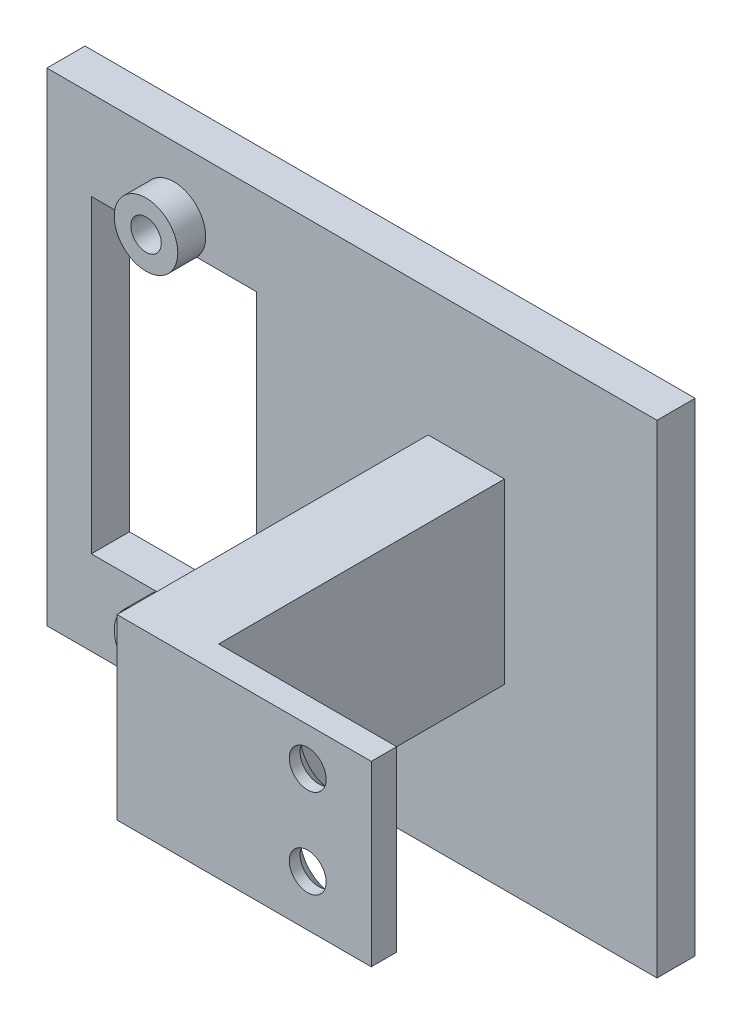
SolidWorks part; units mm, degrees
ref_plane "Front Plane" through (0, 0, 0) normal (0, 0, 1) x (1, 0, 0)
ref_plane "Top Plane" through (0, 0, 0) normal (0, 1, 0) x (1, 0, 0)
ref_plane "Right Plane" through (0, 0, 0) normal (1, 0, 0) x (0, 0, -1)
sketch "Sketch1" plane through (0, 0, 0) normal (0, 0, 1) x (1, 0, 0)
  line L1 (-70, 0) -> (-22, 0)
  line L2 (-70, 0) -> (-70, 38)
  line L3 (-70, 38) -> (-22, 38)
  line L4 (-22, 0) -> (-22, 38)
  line L6 (-66.5, 6.65) -> (-53.5, 6.65)
  line L7 (-66.5, 6.65) -> (-66.5, 31)
  line L8 (-66.5, 31) -> (-53.5, 31)
  line L9 (-53.5, 6.65) -> (-53.5, 31)
extrude "Servo_Shelf" add sketch "Sketch1" along normal blind 3 from offset 27.48 offset against normal yes
sketch "Sketch2" plane through (0, 0, 0) normal (0, 0, 1) x (1, 0, 0)
  line L1 (-40, 14) -> (-34, 14)
  line L2 (-40, 14) -> (-40, 28)
  line L3 (-40, 28) -> (-34, 28)
  line L4 (-34, 14) -> (-34, 28)
extrude "Outboard_Riser" add sketch "Sketch2" along normal blind 24.48 from offset 25.48 offset against normal yes
sketch "Sketch3" plane through (0, 0, 0) normal (0, 0, 1) x (1, 0, 0)
  line L1 (-40, 14) -> (-20, 14)
  line L2 (-40, 14) -> (-40, 28)
  line L3 (-40, 28) -> (-20, 28)
  line L4 (-20, 14) -> (-20, 28)
extrude "Plate_Attachment_Foot" add sketch "Sketch3" along normal blind 2 from offset 2 offset against normal yes
sketch "Sketch4" plane through (0, 0, -2) normal (0, 0, -1) x (-1, 0, 0)
  circle A0 centre (25, 18) radius 1.45
  circle A1 centre (25, 25) radius 1.45
extrude "Servo_Pad_D2p9" cut sketch "Sketch4" against normal blind 2.01
sketch "Sketch5" plane through (0, 0, -2) normal (0, 0, -1) x (-1, 0, 0)
  circle A0 centre (25, 18) radius 2.6
  circle A1 centre (25, 25) radius 2.6
extrude "Servo_Pad_CSK_D5p2_90deg" cut sketch "Sketch5" against normal blind 1.15 draft 45
sketch "Sketch6" plane through (0, 0, 0) normal (0, 0, 1) x (1, 0, 0)
  circle A0 centre (-60, 4.55) radius 2.5
  circle A1 centre (-60, 32.75) radius 2.5
extrude "Servo_Ear_Supports_H2p2" add sketch "Sketch6" along normal blind 2.2 from offset 24.48 offset against normal yes
sketch "Sketch7" plane through (0, 0, -22.28) normal (0, 0, 1) x (1, 0, 0)
  circle A0 centre (-60, 4.55) radius 1.2
  circle A1 centre (-60, 32.75) radius 1.2
extrude "Servo_Ear_D2p4_Through" cut sketch "Sketch7" against normal blind 5.21
